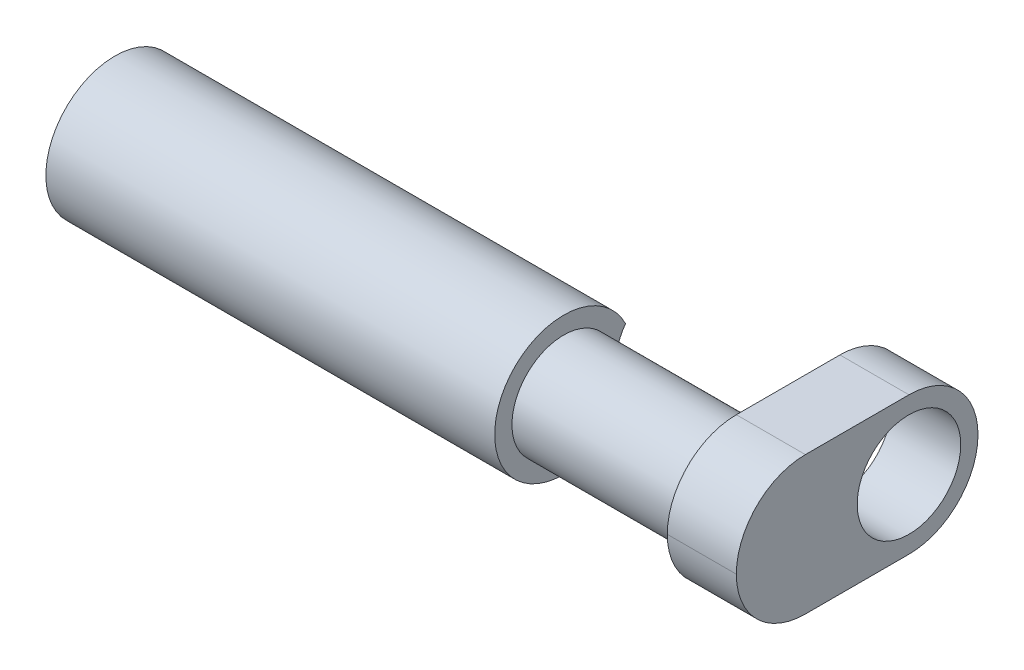
SolidWorks part; units mm, degrees
material "Nickel"
ref_plane "Front Plane" through (0, 0, 0) normal (0, 0, 1) x (1, 0, 0)
ref_plane "Top Plane" through (0, 0, 0) normal (0, 1, 0) x (1, 0, 0)
ref_plane "Right Plane" through (0, 0, 0) normal (1, 0, 0) x (0, 0, -1)
sketch "Sketch2" plane through (0, 0, 0) normal (1, 0, 0) x (0, 0, -1)
  circle A0 centre (0, 0) radius 2
  dimension "D1" = 4
extrude "Boss-Extrude1" add sketch "Sketch2" along normal blind 13
sketch "Sketch3" plane through (13, 0, 0) normal (1, 0, 0) x (0, 0, -1)
  circle A0 centre (0, 0) radius 1.5
  dimension "D1" = 3
extrude "Boss-Extrude2" add sketch "Sketch3" along normal blind 7
sketch "Sketch4" plane through (20, 0, 0) normal (1, 0, 0) x (0, 0, -1)
  line L1 (-2, 2) -> (1.9881, 2)
  line L2 (-2, 2) -> (-2, -2)
  line L3 (-2, -2) -> (1.9881, -2)
  line L4 (1.9881, 2) -> (1.9881, -2)
  circle A0 centre (0, 0) radius 2 construction
extrude "Boss-Extrude3" add sketch "Sketch4" against normal blind 2
sketch "Sketch5" plane through (0, 0, 2) normal (0, 0, 1) x (1, 0, 0)
  line L1 (20, 2) -> (18, 2)
  line L2 (20, 2) -> (20, -2)
  line L3 (20, -2) -> (18, -2)
  line L4 (18, 2) -> (18, -2)
extrude "Boss-Extrude4" add sketch "Sketch5" against normal blind 7
fillet "Fillet1" radius 2 1 edges at (19, 2, 2)
fillet "Fillet2" radius 2 1 edges at (19, -2, 2)
fillet "Fillet3" radius 2 2 edges at (19, -2, -5) (19, 2, -5)
sketch "Sketch6" plane through (20, 0, 0) normal (1, 0, 0) x (0, 0, -1)
  circle A0 centre (3, 0) radius 1.5
  point P2 (3, 0)
  point P5 (3, 0)
  dimension "D1" = 3
extrude "Cut-Extrude1" cut sketch "Sketch6" against normal through all
